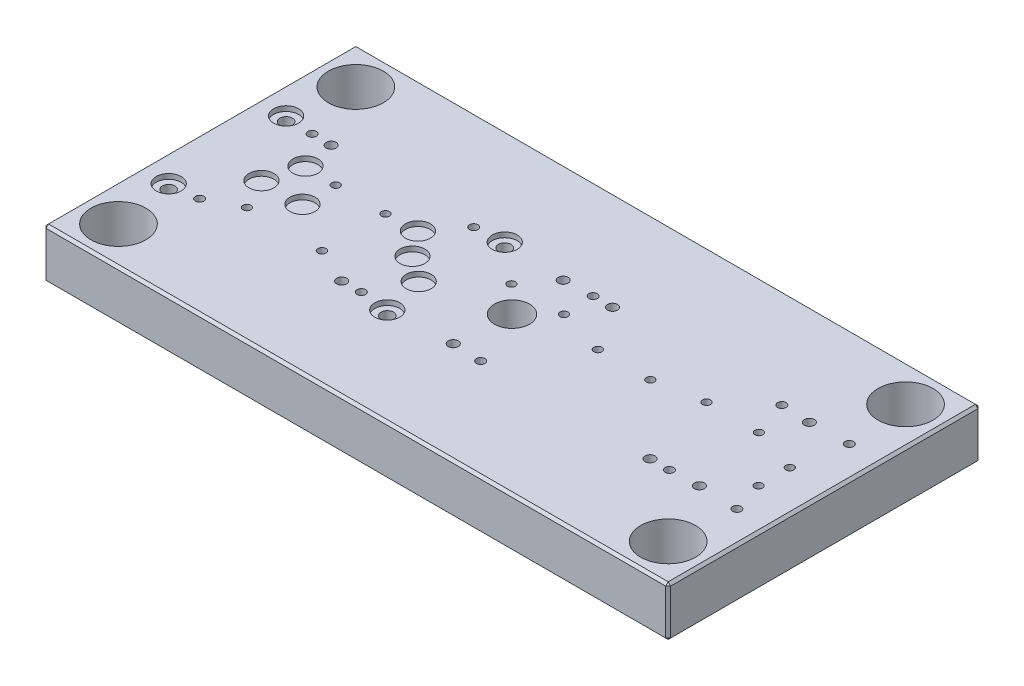
SolidWorks part; units mm, degrees
material "Plain Carbon Steel"
ref_plane "Front Plane" through (0, 0, 0) normal (0, 0, 1) x (1, 0, 0)
ref_plane "Top Plane" through (0, 0, 0) normal (0, 1, 0) x (1, 0, 0)
ref_plane "Right Plane" through (0, 0, 0) normal (1, 0, 0) x (0, 0, -1)
sketch "Sketch2" plane through (0, 0, 0) normal (0, 1, 0) x (1, 0, 0)
  line L1 (-250, -62.5) -> (250, -62.5)
  line L2 (-250, -62.5) -> (-250, 62.5)
  line L3 (-250, 62.5) -> (250, 62.5)
  line L4 (250, -62.5) -> (250, 62.5)
  line L5 (-250, -62.5) -> (250, 62.5) construction
  line L6 (-250, 62.5) -> (250, -62.5) construction
  point P0 (0, 0)
  dimension "D1" = 500
  dimension "D2" = 125
extrude "Boss-Extrude1" add sketch "Sketch2" along normal blind 40
sketch "Sketch5" plane through (0, 0, 0) normal (0, -1, 0) x (-1, 0, 0)
  line L4 (-250, 62.5) -> (-250, -62.5)
  line L5 (250, 62.5) -> (-250, 62.5)
  line L6 (250, -62.5) -> (250, 62.5)
  line L7 (-250, -62.5) -> (250, -62.5)
  line L8 (-250, 62.5) -> (-250, -62.5) construction
  line L9 (250, 62.5) -> (-250, 62.5) construction
  line L10 (250, -62.5) -> (250, 62.5) construction
  line L11 (-250, -62.5) -> (250, -62.5) construction
  dimension "D1" = 0
sketch "Sketch3" plane through (0, 0, -62.5) normal (0, 0, -1) x (-1, 0, 0)
  line L4 (-250, 0) -> (250, 0)
  line L5 (-250, 40) -> (-250, 0)
  line L6 (250, 40) -> (-250, 40)
  line L7 (250, 0) -> (250, 40)
  line L8 (-250, 0) -> (250, 0)
  line L9 (-250, 40) -> (-250, 0)
  line L10 (250, 40) -> (-250, 40)
  line L11 (250, 0) -> (250, 40)
  dimension "D1" = 0
extrude "Boss-Extrude2" add sketch "Sketch3" along normal blind 125
sketch "Sketch6" plane through (0, 0, 0) normal (0, -1, 0) x (-1, 0, 0)
  line L0 (-250, -62.5) -> (-250, 187.5) construction
  line L1 (250, -62.5) -> (-250, -62.5) construction
  line L2 (250, 187.5) -> (-250, 187.5) construction
  circle A0 centre (-220, 157.5) radius 22
  circle A1 centre (-220, -32.5) radius 22
  dimension "D1" = 44
  dimension "D2" = 30
  dimension "D3" = 30
  dimension "D4" = 30
extrude "Cut-Extrude1" cut sketch "Sketch6" against normal through all
mirror "Mirror1" about plane through (0, 0, 0) normal (1, 0, 0) of "Cut-Extrude1"
hole_wizard "M30x2.0 Tapped Hole1" positions "Sketch10" profile "Sketch9" tap size "M30x2.0" standard "ISO" end condition through all
sketch "Sketch10" plane through (0, 40, 0) normal (0, 1, 0) x (1, 0, 0)
  line L0 (-250, 187.5) -> (-250, -62.5) construction
  point P0 (0, 62.5)
  point P8 (-250, 62.5)
sketch "Sketch9" plane through (0, 40, -62.5) normal (1, 0, 0) x (0, 0, 1)
  line L0 (0, 0) -> (0, 40)
  line L1 (0, 40) -> (14, 40)
  line L2 (14, 40) -> (14, 0)
  line L5 (14, 0) -> (0, 0)
  line L11 (0, -6.35) -> (0, 107.95) construction
  dimension "Thru Tap Drill Dia." = 28
  dimension "Thru Tap Drill Depth" = 40
cosmetic thread "Hole Thread1"
chamfer "Chamfer1" distance 2 angle 45 12 edges at (250, 40, -62.5) (250, 0, -62.5) (0, 40, -187.5) (250, 20, -187.5) (0, 0, -187.5) (-250, 40, -62.5) (-250, 20, -187.5) (-250, 0, -62.5) (250, 20, 62.5) (0, 40, 62.5) (-250, 20, 62.5) (0, 0, 62.5)
hole_wizard "M8 Tapped Hole1" positions "Sketch34" profile "Sketch12" tap size "M8" standard "ISO" end condition through all
sketch "Sketch34" plane through (0, 0, 0) normal (0, -1, 0) x (-1, 0, 0)
  point P0 (-171, 17.5)
  point P3 (-19.969, 17.5)
  point P6 (-19.969, 107.5)
  point P9 (-171, 107.5)
  point P12 (75.6325, 107.5)
  point P15 (205, 107.5)
  point P18 (205, 17.5)
  point P21 (75.6325, 17.5)
sketch "Sketch12" plane through (171, 0, -17.5) normal (1, 0, 0) x (0, 0, -1)
  line L0 (0, 0) -> (0, 40)
  line L1 (0, 40) -> (3.4, 40)
  line L2 (3.4, 40) -> (3.4, 0)
  line L5 (3.4, 0) -> (0, 0)
  line L11 (0, -6.35) -> (0, 107.95) construction
  dimension "Thru Tap Drill Dia." = 6.8
  dimension "Thru Tap Drill Depth" = 40
hole_wizard "Ø8.0mm Dowel Hole1" positions "Sketch16" profile "Sketch15" hole size "Ø8.0" standard "ISO" end condition through all
sketch "Sketch16" plane through (0, 0, 0) normal (0, -1, 0) x (-1, 0, 0)
  point P0 (-155.5, 17.5)
  point P3 (-35.469, 107.5)
  point P6 (91.1325, 17.259)
  point P9 (189.5, 107.2284)
sketch "Sketch15" plane through (155.5, 0, -17.5) normal (1, 0, 0) x (0, 0, -1)
  line L0 (0, 0) -> (0, 40)
  line L1 (0, 40) -> (4, 40)
  line L2 (4, 40) -> (4, 0)
  line L5 (4, 0) -> (0, 0)
  line L11 (0, -6.35) -> (0, 107.95) construction
  dimension "Thru Hole Dia." = 8
  dimension "Thru Hole Depth" = 40
hole_wizard "CBORE for M6 Hex Socket Head Cap Screw1" positions "Sketch48" profile "Sketch18" counterbore size "M6" standard "ISO" end condition through all
sketch "Sketch48" plane through (0, 0, 0) normal (0, -1, 0) x (-1, 0, 0)
  point P0 (-180.875, 79.28)
  point P6 (-100.875, 72.3524)
  point P9 (-58.875, 72.3524)
  point P12 (-20.875, 83.191)
  point P17 (-138.875, 79.28)
  point P20 (21.125, 83.191)
  point P24 (-217.6, 42.28)
  point P27 (-217.6, 67.28)
sketch "Sketch18" plane through (180.875, 0, -79.28) normal (1, 0, 0) x (0, 0, -1)
  line L0 (0, 0) -> (0, 40)
  line L1 (0, 40) -> (3.2, 40)
  line L3 (3.2, 40) -> (3.2, 6.4)
  line L4 (3.2, 6.4) -> (5.5, 6.4)
  line L5 (5.5, 6.4) -> (5.5, 0)
  line L7 (5.5, 0) -> (0, 0)
  line L11 (0, -6.35) -> (0, 107.95) construction
  dimension "Thru Hole Dia." = 6.4
  dimension "Thru Hole Depth" = 40
  dimension "C'Bore Dia." = 11
  dimension "C'Bore Depth" = 6.4
hole_wizard "CBORE for M6 Hex Socket Head Cap Screw2" positions "Sketch24" profile "Sketch23" counterbore size "M6" standard "ISO" end condition through all
sketch "Sketch24" plane through (0, 0, 0) normal (0, -1, 0) x (-1, 0, 0)
  point P0 (160, 81.36)
  point P3 (120.125, 81.36)
  point P6 (120, 30.34)
  point P9 (180, 30.34)
sketch "Sketch23" plane through (-160, 0, -81.36) normal (1, 0, 0) x (0, 0, -1)
  line L0 (0, 0) -> (0, 40)
  line L1 (0, 40) -> (3.2, 40)
  line L3 (3.2, 40) -> (3.2, 6.4)
  line L4 (3.2, 6.4) -> (5.5, 6.4)
  line L5 (5.5, 6.4) -> (5.5, 0)
  line L7 (5.5, 0) -> (0, 0)
  line L11 (0, -6.35) -> (0, 107.95) construction
  dimension "Thru Hole Dia." = 6.4
  dimension "Thru Hole Depth" = 40
  dimension "C'Bore Dia." = 11
  dimension "C'Bore Depth" = 6.4
sketch "Sketch25" plane through (0, 40, 0) normal (0, 1, 0) x (1, 0, 0)
  circle A0 centre (-227.8163, 15.5) radius 10 construction
  circle A1 centre (-52.8163, 15.5) radius 10 construction
  circle A2 centre (-52.8163, 109.5) radius 10 construction
  circle A3 centre (-227.8163, 109.5) radius 10 construction
  circle A4 centre (-185.3163, 82.5) radius 10 construction
  circle A5 centre (-192.8163, 54.78) radius 10 construction
  circle A6 centre (-160, 54.78) radius 10 construction
  circle A7 centre (-95.3163, 82.5) radius 10 construction
  circle A8 centre (-80, 62.78) radius 10 construction
  circle A9 centre (-60, 47.78) radius 10 construction
  circle A10 centre (-227.8163, 15.5) radius 10
  circle A11 centre (-52.8163, 15.5) radius 10
  circle A12 centre (-52.8163, 109.5) radius 10
  circle A13 centre (-227.8163, 109.5) radius 10
  circle A14 centre (-185.3163, 82.5) radius 10
  circle A15 centre (-192.8163, 54.78) radius 10
  circle A16 centre (-160, 54.78) radius 10
  circle A17 centre (-95.3163, 82.5) radius 10
  circle A18 centre (-80, 62.78) radius 10
  circle A19 centre (-60, 47.78) radius 10
extrude "Cut-Extrude2" cut sketch "Sketch25" against normal blind 4
hole_wizard "Ø10.0 (10) Diameter Hole1" positions "Sketch33" profile "Sketch28" hole size "Ø10.0" standard "ISO" end condition through all
sketch "Sketch33" plane through (0, 40, 0) normal (0, 1, 0) x (1, 0, 0)
  point P0 (-52.8163, 15.5)
  point P18 (-227.8163, 109.5)
  point P21 (-227.8163, 15.5)
  point P24 (-52.8163, 109.5)
sketch "Sketch28" plane through (-52.8163, 40, -15.5) normal (1, 0, 0) x (0, 0, 1)
  line L0 (0, 0) -> (0, 40)
  line L1 (0, 40) -> (5, 40)
  line L2 (5, 40) -> (5, 0)
  line L5 (5, 0) -> (0, 0)
  line L11 (0, -6.35) -> (0, 107.95) construction
  dimension "Thru Hole Dia." = 10
  dimension "Thru Hole Depth" = 40
sketch "Sketch35" plane through (0, 0, 0) normal (0, -1, 0) x (1, 0, 0)
  circle A0 centre (-52.8163, -109.5) radius 8.5
  circle A1 centre (-227.8163, -15.5) radius 8.5
  circle A2 centre (-227.8163, -109.5) radius 8.5
  circle A3 centre (-52.8163, -15.5) radius 8.5
  dimension "D1" = 17
extrude "Cut-Extrude3" cut sketch "Sketch35" against normal blind 24
hole_wizard "Ø8.0 (8) Diameter Hole2" positions "Sketch42" profile "Sketch41" hole size "Ø8.0" standard "ISO" end condition through all
sketch "Sketch42" plane through (0, 40, 0) normal (0, 1, 0) x (1, 0, 0)
  point P0 (-3.031, 106.5)
  point P3 (-3.031, 18.5)
  point P6 (194, 106.5)
  point P9 (194, 18.5)
sketch "Sketch41" plane through (-3.031, 40, -106.5) normal (1, 0, 0) x (0, 0, 1)
  line L0 (0, 0) -> (0, 40)
  line L1 (0, 40) -> (4, 40)
  line L2 (4, 40) -> (4, 0)
  line L5 (4, 0) -> (0, 0)
  line L11 (0, -6.35) -> (0, 107.95) construction
  dimension "Thru Hole Dia." = 8
  dimension "Thru Hole Depth" = 40
sketch "Sketch43" plane through (0, 0, 0) normal (0, -1, 0) x (1, 0, 0)
  circle A0 centre (194, -106.5) radius 7
  circle A1 centre (194, -18.5) radius 7
  circle A2 centre (-3.031, -18.5) radius 7
  circle A3 centre (-3.031, -106.5) radius 7
  dimension "D1" = 14
extrude "Cut-Extrude4" cut sketch "Sketch43" against normal blind 32
hole_wizard "M8 Tapped Hole2" positions "Sketch46" profile "Sketch45" tap size "M8" standard "ISO" end condition through all
sketch "Sketch46" plane through (0, 0, 0) normal (0, -1, 0) x (-1, 0, 0)
  point P0 (-225, 107.5)
  point P3 (-225, 17.5)
sketch "Sketch45" plane through (225, 0, -107.5) normal (1, 0, 0) x (0, 0, -1)
  line L0 (0, 0) -> (0, 40)
  line L1 (0, 40) -> (3.4, 40)
  line L2 (3.4, 40) -> (3.4, 0)
  line L5 (3.4, 0) -> (0, 0)
  line L11 (0, -6.35) -> (0, 107.95) construction
  dimension "Thru Tap Drill Dia." = 6.8
  dimension "Thru Tap Drill Depth" = 40
cosmetic thread "Hole Thread2"
cosmetic thread "Hole Thread3"
